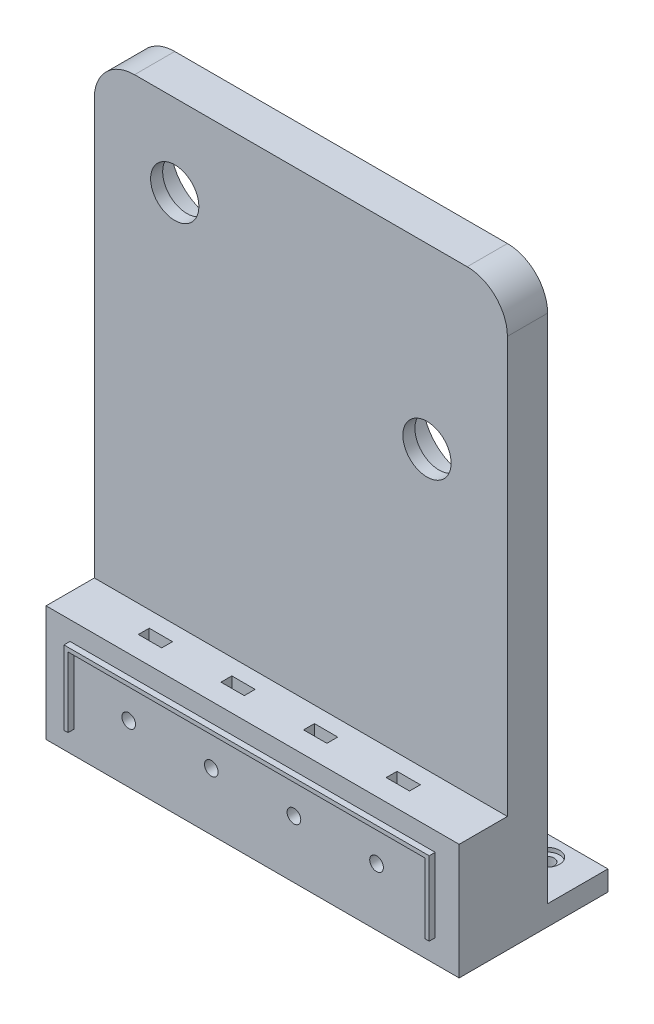
SolidWorks part; units mm, degrees
ref_plane "Front Plane" through (0, 0, 0) normal (0, 0, 1) x (1, 0, 0)
ref_plane "Top Plane" through (0, 0, 0) normal (0, 1, 0) x (1, 0, 0)
ref_plane "Right Plane" through (0, 0, 0) normal (1, 0, 0) x (0, 0, -1)
sketch "Sketch2" plane through (0, 0, 0) normal (0, 0, 1) x (1, 0, 0)
  line L1 (-10, 0) -> (-92.7384, 0)
  line L2 (0, -10) -> (0, -142.2022)
  line L3 (0, -142.2022) -> (-102.7384, -142.2022)
  line L4 (-102.7384, -10) -> (-102.7384, -142.2022)
  circle A0 centre (-82.7384, -20.4) radius 11.05
  circle A1 centre (-20, -44.2985) radius 11.05
  arc A2 (-10, 0) -> (0, -10) centre (-10, -10) cw
  arc A3 (-92.7384, 0) -> (-102.7384, -10) centre (-92.7384, -10) ccw
  circle A4 centre (-82.7384, -20.4) radius 6
  circle A5 centre (-20, -44.2985) radius 6
  point P11 (0, 0)
  dimension "D5" = 22.1
  dimension "D8" = 10
  dimension "D9" = 12
  dimension "D1" = 62.7384
  dimension "D2" = 20
  dimension "D3" = 20
  dimension "D4" = 20.4
  dimension "D6" = 97.9038
  dimension "D7" = 23.8985
extrude "Boss-Extrude2" add sketch "Sketch2" along normal blind 10 contours L1 A3 L4 L3 L2 A2 A0 A1 region at (-51.3692, -73.4697, 0)
extrude "Boss-Extrude3" add sketch "Sketch2<4>" along normal blind 3 from offset 7 contours A0 A4 | A1 A5 region at (-93.4759, -20.4, 0) region at (-30.7375, -44.2985, 0)
sketch "Sketch2<4>" plane through (0, 0, 0) normal (0, 0, 1) x (1, 0, 0) same geometry as "Sketch2"
sketch "Sketch3" plane through (0, 0, 10) normal (0, 0, 1) x (1, 0, 0)
  line L0 (0, -10) -> (0, -142.2022) construction
  line L1 (-102.7384, -142.2022) -> (0, -142.2022)
  line L2 (-102.7384, -142.2022) -> (-102.7384, -113.4022)
  line L3 (-102.7384, -113.4022) -> (0, -113.4022)
  line L4 (0, -142.2022) -> (0, -113.4022)
  dimension "D1" = 28.8
extrude "Boss-Extrude4" add sketch "Sketch3" along normal blind 12
sketch "Sketch4" plane through (0, 0, 22) normal (0, 0, 1) x (1, 0, 0)
  line L0 (-82.1908, -127.8522) -> (-61.6431, -127.8522) construction
  line L1 (-102.7384, -113.4022) -> (-102.7384, -142.2022) construction
  line L3 (0, -113.4022) -> (-102.7384, -113.4022) construction
  line L4 (-64.5431, -131.1522) -> (-58.7431, -131.1522)
  line L5 (-85.0908, -131.1522) -> (-79.2908, -131.1522)
  line L6 (-85.0908, -131.1522) -> (-85.0908, -113.4022)
  line L7 (-85.0908, -113.4022) -> (-79.2908, -113.4022)
  line L8 (-79.2908, -131.1522) -> (-79.2908, -113.4022)
  line L9 (-64.5431, -131.1522) -> (-64.5431, -113.4022)
  line L10 (-64.5431, -113.4022) -> (-58.7431, -113.4022)
  line L11 (-58.7431, -131.1522) -> (-58.7431, -113.4022)
  line L12 (-43.9954, -131.1522) -> (-38.1954, -131.1522)
  line L13 (-43.9954, -131.1522) -> (-43.9954, -113.4022)
  line L14 (-43.9954, -113.4022) -> (-38.1954, -113.4022)
  line L15 (-38.1954, -131.1522) -> (-38.1954, -113.4022)
  line L16 (-23.4477, -131.1522) -> (-17.6477, -131.1522)
  line L17 (-23.4477, -131.1522) -> (-23.4477, -113.4022)
  line L18 (-23.4477, -113.4022) -> (-17.6477, -113.4022)
  line L19 (-17.6477, -131.1522) -> (-17.6477, -113.4022)
  circle A0 centre (-82.1908, -127.8522) radius 1.7
  circle A1 centre (-61.6431, -127.8522) radius 1.7
  circle A2 centre (-41.0954, -127.8522) radius 1.7
  circle A3 centre (-20.5477, -127.8522) radius 1.7
  point P18 (-82.1908, -131.1522)
  point P23 (-61.6431, -131.1522)
  point P28 (-41.0954, -131.1522)
  point P33 (-20.5477, -131.1522)
  dimension "D1" = 3.4
  dimension "D4" = 20.5477
  dimension "D5" = 14.45
  dimension "D3" = 20.5477
  dimension "D6" = 5.8
  dimension "D7" = 3.3
  dimension "D2" = 4
extrude "Cut-Extrude2" cut sketch "Sketch4" against normal blind 8 contours L7 L8 L5 L6 | L9 L10 L11 L4 | L13 L14 L15 L12 | L17 L18 L19 L16
extrude "Boss-Extrude5" add sketch "Sketch4<7>" against normal blind 5.3
sketch "Sketch4<7>" plane through (0, 0, 22) normal (0, 0, 1) x (1, 0, 0) same geometry as "Sketch4"
sketch "Sketch5" plane through (0, 0, 22) normal (0, 0, 1) x (1, 0, 0)
  line L5 (-102.7384, -113.4022) -> (-102.7384, -142.2022) construction
  line L11 (-95.7884, -136.5022) -> (-96.7884, -136.5022)
  line L12 (-96.7884, -118.1022) -> (-5.95, -118.1022)
  line L13 (-5.95, -136.5022) -> (-5.95, -118.1022)
  line L14 (-6.95, -136.5022) -> (-5.95, -136.5022)
  line L15 (-96.7884, -118.1022) -> (-96.7884, -136.5022)
  line L16 (-95.7884, -136.5022) -> (-95.7884, -119.1022)
  line L17 (-6.95, -119.1022) -> (-6.95, -136.5022)
  line L18 (-6.95, -119.1022) -> (-95.7884, -119.1022)
  line L19 (0, -142.2022) -> (0, -113.4022) construction
  point P6 (-96.4884, -117.9375)
  point P7 (-6.95, -127.8022)
  point P11 (0, -127.8022)
  point P16 (-7.25, -118.7022)
  point P17 (-6.25, -117.7022)
  point P18 (-6.25, -136.1022)
  point P19 (-95.4884, -118.7022)
  point P20 (-96.4884, -117.7022)
  point P21 (-96.4884, -130.1708)
  point P22 (0, 0)
  dimension "D1" = 6.95
  dimension "D2" = 6.95
  dimension "D3" = 1
  dimension "D4" = 17.4
  dimension "D5" = 1
  dimension "D6" = 1
extrude "Boss-Extrude6" add sketch "Sketch5" along normal blind 1.5
sketch "Sketch6" plane through (0, -142.2022, 0) normal (0, -1, 0) x (1, 0, 0)
  line L1 (-102.7384, -15) -> (0, -15)
  line L2 (-102.7384, -15) -> (-102.7384, 10)
  line L3 (-102.7384, 10) -> (0, 10)
  line L4 (0, -15) -> (0, 10)
  line L5 (-102.7384, 22) -> (-102.7384, 0) construction
  line L6 (0, 22) -> (0, 0) construction
  line L7 (0, 10) -> (-102.7384, 10) construction
  dimension "D1" = 25
extrude "Boss-Extrude7" add sketch "Sketch6" against normal blind 5
sketch "Sketch7" plane through (-101.6402, -137.2022, -23.0528) normal (0, 1, 0) x (-1, 0, 0)
  line L4 (-101.6402, 8.0528) -> (-101.6402, 23.0528) construction
  line L5 (1.0982, 23.0528) -> (1.0982, 8.0528) construction
  line L6 (1.0982, 8.0528) -> (-101.6402, 8.0528) construction
  line L7 (-101.6402, 23.0528) -> (1.0982, 23.0528) construction
  circle A0 centre (-91.6402, 13.0528) radius 1.65
  circle A1 centre (-50.271, 18.0528) radius 1.65
  circle A2 centre (-8.9018, 13.0528) radius 1.65
  circle A3 centre (-91.6402, 13.0528) radius 3
  circle A4 centre (-50.271, 18.0528) radius 3
  circle A5 centre (-8.9018, 13.0528) radius 3
  point P20 (-50.271, 8.0528)
  dimension "D1" = 3.3
  dimension "D2" = 6
  dimension "D5" = 5
  dimension "D3" = 10
  dimension "D4" = 10
  dimension "D6" = 5
extrude "Cut-Extrude3" cut sketch "Sketch7" against normal blind 5 contours A0 | A1 | A2
extrude "Cut-Extrude4" cut sketch "Sketch7<6>" against normal blind 1
sketch "Sketch7<6>" plane through (-101.6402, -137.2022, -23.0528) normal (0, 1, 0) x (-1, 0, 0) same geometry as "Sketch7"
